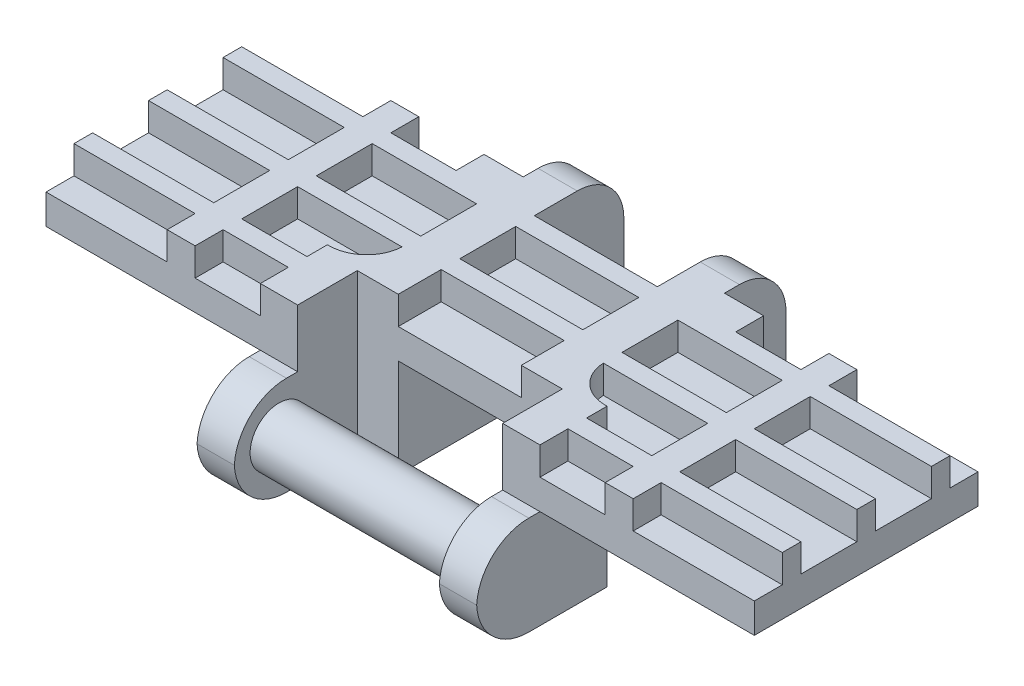
SolidWorks part; units mm, degrees
ref_plane "前视基准面" through (0, 0, 0) normal (0, 0, 1) x (1, 0, 0)
ref_plane "上视基准面" through (0, 0, 0) normal (0, 1, 0) x (1, 0, 0)
ref_plane "右视基准面" through (0, 0, 0) normal (1, 0, 0) x (0, 0, -1)
other "Configuration Table"
sketch "草图1" plane through (0, 0, 0) normal (0, 1, 0) x (1, 0, 0)
  line L1 (-19, -6) -> (19, -6)
  line L2 (-19, -6) -> (-19, 6)
  line L3 (-19, 6) -> (19, 6)
  line L4 (19, -6) -> (19, 6)
  line L5 (-19, -6) -> (19, 6) construction
  line L6 (-19, 6) -> (19, -6) construction
  line L13 (-19, 4.5) -> (19, 4.5)
  line L14 (-19, 4.5) -> (-19, 3.5)
  line L15 (-19, 3.5) -> (19, 3.5)
  line L16 (19, 4.5) -> (19, 3.5)
  line L17 (-19, 0.5) -> (19, 0.5)
  line L18 (-19, 0.5) -> (-19, -0.5)
  line L19 (-19, -0.5) -> (19, -0.5)
  line L20 (19, 0.5) -> (19, -0.5)
  line L21 (-19, -3.5) -> (19, -3.5)
  line L22 (-19, -3.5) -> (-19, -4.5)
  line L23 (-19, -4.5) -> (19, -4.5)
  line L24 (19, -3.5) -> (19, -4.5)
  line L25 (-12.5, 6) -> (-11, 6)
  line L26 (-12.5, 6) -> (-12.5, -6)
  line L27 (-12.5, -6) -> (-11, -6)
  line L28 (-11, 6) -> (-11, -6)
  line L29 (12.5, 6) -> (11, 6)
  line L30 (12.5, 6) -> (12.5, -6)
  line L31 (12.5, -6) -> (11, -6)
  line L32 (11, 6) -> (11, -6)
  point P0 (0, 0)
  point P6 (0, 0)
  dimension "D1" = 38
  dimension "D2" = 12
  dimension "D3" = 11
  dimension "D4" = 11
  dimension "D5" = 1
  dimension "D6" = 1.5
  dimension "D7" = 1.5
  dimension "D8" = 5.5
  dimension "D9" = 1.5
extrude "凸台-拉伸1" add sketch "草图1" along normal blind 1.6 contours L2 L3 L4 L1
extrude "凸台-拉伸2" add sketch "草图1<3>" along normal blind 1.5 from surface contours L13 L16 L15 L14 | L17 L20 L19 L18 | L21 L24 L23 L22 | L26 L27 L28 L25 | L30 L31 L32 L29 starting at face at (0, 1.6, 0)
sketch "草图1<3>" plane through (0, 0, 0) normal (0, 1, 0) x (1, 0, 0) same geometry as "草图1"
sketch "草图2" plane through (0, 0, 0) normal (0, 1, 0) x (1, 0, 0)
  line L0 (0, 0) -> (0, -13.8005) construction
  line L1 (-5.4, 9.3) -> (5.4, 9.3)
  line L2 (-5.4, 9.3) -> (-5.4, -2.8)
  line L3 (-5.4, -2.8) -> (5.4, -2.8)
  line L4 (5.4, 9.3) -> (5.4, -2.8)
  line L5 (-7.5, -2.8) -> (7.5, -2.8)
  line L6 (11, 4.5) -> (-11, 4.5) construction
  line L7 (-7.5, 6) -> (-5.4, 6)
  line L8 (-3.3, 9.3) -> (3.3, 9.3)
  line L9 (-3.3, 9.3) -> (-3.3, -2.8)
  line L10 (-3.3, -2.8) -> (3.3, -2.8)
  line L11 (3.3, 9.3) -> (3.3, -2.8)
  line L16 (-11, -6) -> (11, -6) construction
  line L17 (-11, 6) -> (11, 6) construction
  line L18 (-5.5, -2.4) -> (-5.5, -9.4)
  line L19 (-7.5, -2.4) -> (7.5, -2.4)
  line L20 (-7.5, -2.4) -> (-7.5, -9.4)
  line L21 (-7.5, -9.4) -> (7.5, -9.4)
  line L22 (7.5, -2.4) -> (7.5, -9.4)
  line L23 (5.5, -2.4) -> (5.5, -9.4)
  line L24 (-7.5, 6) -> (-7.5, 4.5)
  line L25 (-7.5, 4.5) -> (-5.4, 4.5)
  line L26 (-5.4, 6) -> (-5.4, 4.5)
  line L27 (7.5, 6) -> (5.4, 6)
  line L28 (7.5, 6) -> (7.5, 4.5)
  line L29 (7.5, 4.5) -> (5.4, 4.5)
  line L30 (5.4, 6) -> (5.4, 4.5)
  point P5 (0, -2.8)
  point P15 (0, 9.3)
  point P20 (0, -9.4)
  dimension "D1" = 10.8
  dimension "D2" = 3.2
  dimension "D3" = 6.6
  dimension "D4" = 3.3
  dimension "D5" = 15
  dimension "D6" = 2
  dimension "D7" = 2
  dimension "D8" = 3.4
  dimension "D9" = 7
extrude "凸台-拉伸3" add sketch "草图2" against normal blind 8.4 from surface contours L1 L11 L3 L4 | L9 L1 L2 L3 | L20 L21 L18 L19 | L19 L23 L21 L22 | L19 L18 L5 L2 | L19 L20 L5 L18 | L19 L2 L3 L9 | L19 L11 L3 L4 | L23 L19 L4 L5 | L19 L23 L5 L22 region at (-4.35, 0, -3.45) region at (4.35, 0, -3.45) region at (-4.35, 0, 2.6) region at (4.35, 0, 2.6) region at (-5.45, 0, 2.6) region at (5.45, 0, 2.6) region at (-6.5, 0, 2.6) region at (6.5, 0, 2.6) region at (-6.5, 0, 6.1) region at (6.5, 0, 6.1) starting at face at (0, 3.1, 0)
extrude "凸台-拉伸5" add sketch "草图2<4>" along normal up to surface (3.1 mm away) contours L27 L30 L29 L28 | L7 L26 L25 L24 up to face at (0, 3.1, -2)
sketch "草图2<4>" plane through (0, 0, 0) normal (0, 1, 0) x (1, 0, 0) same geometry as "草图2"
extrude "切除-拉伸1" cut sketch "草图2<3>" along normal through all contours L0 L5 L3 L18 L21 | L10 L0 L21 L23 L5 L3 region at (2.75, 0, 6.1) region at (-2.75, 0, 6.1)
sketch "草图2<3>" plane through (0, 0, 0) normal (0, 1, 0) x (1, 0, 0) same geometry as "草图2"
fillet "圆角1" radius 3 2 edges at (5.4, -2.65, 2.4) (-5.4, -2.65, 2.4)
sketch "草图3" plane through (-5.5, 0, 0) normal (1, 0, 0) x (0, 0, -1)
  line L2 (-7, -2.5) -> (5.58, -2.5)
  line L3 (2.8, -4.1) -> (9.3, -4.1)
  line L4 (2.8, -4.1) -> (2.8, -5.3)
  line L5 (2.8, -5.3) -> (9.3, -5.3)
  line L6 (9.3, -4.1) -> (9.3, -5.3)
  line L7 (-9.4, -5.3) -> (-9.4, 3.1) construction
  line L8 (-6, 3.1) -> (-9.4, 3.1)
  line L9 (-6, 3.1) -> (-6, 0)
  line L10 (-6, 0) -> (-9.4, 0)
  line L11 (-9.4, 3.1) -> (-9.4, 0)
  circle A0 centre (-7, -2.5) radius 1.55
  circle A1 centre (5.58, -2.5) radius 1.7
  dimension "D1" = 3.1
  dimension "D3" = 3.4
  dimension "D7" = 7
  dimension "D2" = 2.5
  dimension "D4" = 1.2
  dimension "D5" = 6.5
  dimension "D6" = 12.58
extrude "凸台-拉伸4" add sketch "草图3" along normal up to next contours A0
extrude "切除-拉伸2" cut sketch "草图3<3>" along normal through all both and the other way through all contours L3 L6 L5 L4 | A1 | L11 L10 L9 L8
sketch "草图3<3>" plane through (-5.5, 0, 0) normal (1, 0, 0) x (0, 0, -1) same geometry as "草图3"
fillet "圆角2" radius 2.8 4 edges at (6.5, -5.3, 9.4) (-6.5, -5.3, 9.4) (-6.5, 0, 9.4) (6.5, 0, 9.4)
fillet "圆角3" radius 2.5 2 edges at (-4.35, 3.1, -9.3) (4.35, 3.1, -9.3)
fillet "圆角4" radius 1 2 edges at (-4.35, -4.1, -9.3) (4.35, -4.1, -9.3)
fillet "圆角5" radius 0.3 4 edges at (-4.35, -4.1, -6.1545) (4.35, -4.1, -6.1545) (4.35, -4.1, -5.0055) (-4.35, -4.1, -5.0055)
fillet "圆角6" radius 2 2 edges at (5.4, 2.35, 2.4) (-5.4, 2.35, 2.4)
